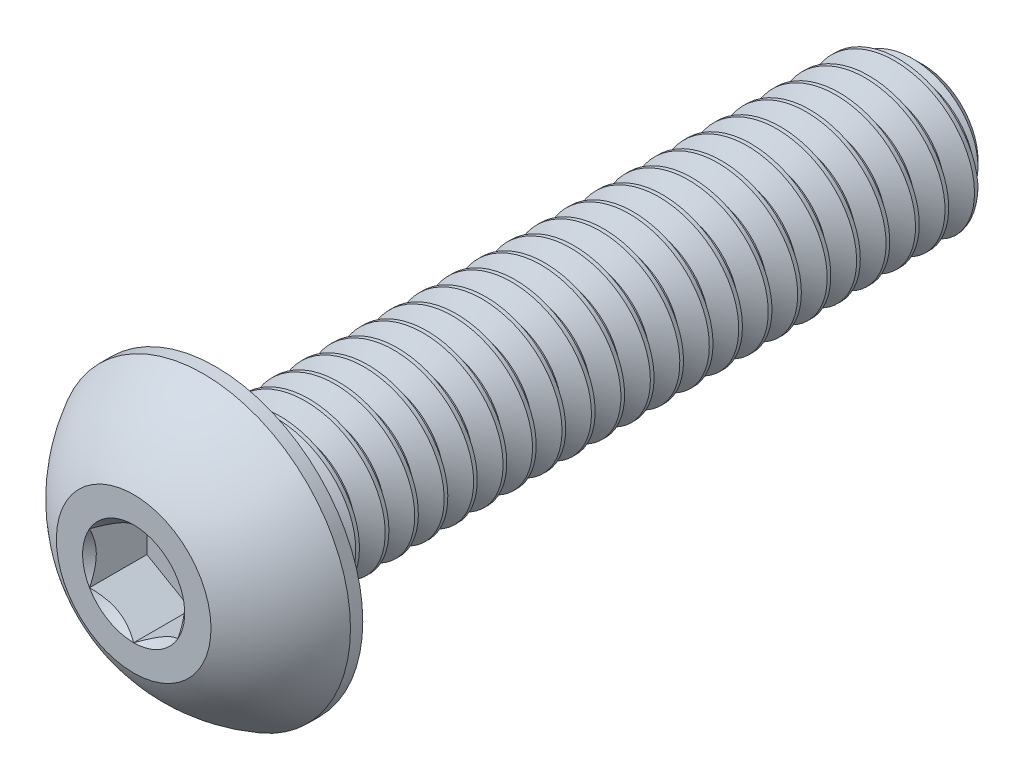
SolidWorks part; units mm, degrees
ref_plane "Front" through (0, 0, 0) normal (0, 0, 1) x (1, 0, 0)
ref_plane "Top" through (0, 0, 0) normal (0, 1, 0) x (1, 0, 0)
ref_plane "Right" through (0, 0, 0) normal (1, 0, 0) x (0, 0, -1)
sketch "Sketch1" plane through (0, 0, 0) normal (1, 0, 0) x (0, 0, -1)
  line L2 (2.2098, 2.0828) -> (21.2598, 2.0828)
  line L3 (21.2598, 2.0828) -> (21.2598, 0)
  line L4 (21.2598, 0) -> (2.2098, 0)
  line L6 (1.8783, 3.9624) -> (2.2098, 3.9624) construction
  line L7 (21.2598, 2.0828) -> (21.2598, -2.0828) construction
  line L8 (0, 0) -> (2.2098, 0) construction
  line L9 (2.2098, 3.9624) -> (2.2098, -3.9624) construction
  line L11 (2.2098, 2.0828) -> (2.2098, 0)
  line L13 (0, 1.1906) -> (0, -1.1906) construction
  line L14 (0, 1.1906) -> (0, 2.0828) construction
  arc A3 (0, 2.0828) -> (1.8783, 3.9624) centre (3.9638, 0) cw construction
  dimension "D1" = 0.3315
revolve "Revolve1" add sketch "Sketch1" angle 360 mid plane about L4
sketch "Sketch3" plane through (0, 0, -21.2598) normal (0, 0, -1) x (-1, 0, 0)
  circle A0 centre (0, 0) radius 2.0828
curve "Helix/Spiral1" pitch 0.7937 height 19.8438 turns 25
sketch "Sketch2" plane through (0, 0, 0) normal (1, 0, 0) x (0, 0, -1)
  line L0 (21.2598, 2.0828) -> (21.9543, 2.0828)
  line L1 (21.9543, 2.0828) -> (21.6567, 1.5672)
  line L2 (21.6567, 1.5672) -> (21.5575, 1.5672)
  line L3 (21.5575, 1.5672) -> (21.2598, 2.0828)
  line L4 (21.4086, 1.825) -> (21.8055, 1.825) construction
  dimension "D1" = 60
  dimension "D2" = 0.0992
  dimension "D3" = 0.3969
chamfer "Chamfer1" distance 0.5953 angle 45 1 edges at (0, 2.0828, -21.2598)
sweep "Cut-Sweep1" cut profiles "Sketch2" path "Helix/Spiral1" align with end faces yes
sketch "Sketch7" plane through (0, 0, 0) normal (1, 0, 0) x (0, 0, -1)
  line L6 (1.8783, 3.9624) -> (2.2098, 3.9624) construction
  line L8 (0, 0) -> (2.2098, 0) construction
  line L11 (2.2098, 3.9624) -> (2.2098, -3.9624) construction
  line L12 (1.8783, 3.9624) -> (2.2098, 3.9624)
  line L13 (0, 0) -> (2.2098, 0)
  line L14 (0, 1.1906) -> (0, -1.1906) construction
  line L15 (2.2098, 3.9624) -> (2.2098, 0)
  line L16 (0, 2.0828) -> (0, 0)
  arc A2 (1.8783, 3.9624) -> (0, 2.0828) centre (3.9638, 0) ccw construction
  arc A3 (1.8783, 3.9624) -> (0, 2.0828) centre (3.9638, 0) ccw
revolve "Revolve2" add sketch "Sketch7" angle 360 mid plane about L13
sketch "Sketch5" plane through (0, 0, 0) normal (0, 0, 1) x (1, 0, 0)
  line L1 (1.1906, -0.6874) -> (1.1906, 0.6874)
  line L2 (1.1906, 0.6874) -> (0, 1.3748)
  line L3 (0, 1.3748) -> (-1.1906, 0.6874)
  line L4 (-1.1906, 0.6874) -> (-1.1906, -0.6874)
  line L5 (-1.1906, -0.6874) -> (0, -1.3748)
  line L6 (0, -1.3748) -> (1.1906, -0.6874)
  circle A0 centre (0, 0) radius 1.1906 construction
extrude "Cut-Extrude2" cut sketch "Sketch5" against normal blind 1.5469
sketch "Sketch6" plane through (0, 0, 0) normal (0, 0, 1) x (1, 0, 0)
  circle A0 centre (0, 0) radius 1.3748
extrude "Cut-Extrude3" cut sketch "Sketch6" against normal blind 1.5469 draft 45
sketch "Sketch9" [suppressed] plane through (0, 0, -1.4986) normal (0, 0, 1) x (1, 0, 0)
  circle A2 centre (0, 0) radius 1.4224
extrude "Boss-Extrude2" [suppressed] add sketch "Sketch9" against normal offset from surface (12.7 mm away) 31.75
sketch "Sketch10" plane through (0, 0, 0) normal (1, 0, 0) x (0, 0, -1)
  line L0 (21.2598, 2.0828) -> (21.2598, -2.0828) construction
  point P0 (20.0692, -2.0828)
  dimension "D1" = 1.1906
equation "\"D3@Helix/Spiral1\" = \"Lg@Sketch1\" + \"D4@Helix/Spiral1\""
equation "\"D2@Sketch2\" = \"D4@Helix/Spiral1\" * .125"
equation "\"D3@Sketch2\" = \"D4@Helix/Spiral1\" * .5"
equation "\"D1@Chamfer1\" = \"D4@Helix/Spiral1\" * .75"
equation "\"D1@Cut-Extrude2\" = \"Head Ht@Sketch1\" * .7"
equation "\"D1@Sketch1\" = \"Head Ht@Sketch1\" * .15"
equation "\"D1@Sketch10\" = \"D4@Helix/Spiral1\" * 1.5"
equation "\"D1@Cut-Extrude3\" = \"D1@Cut-Extrude2\""
